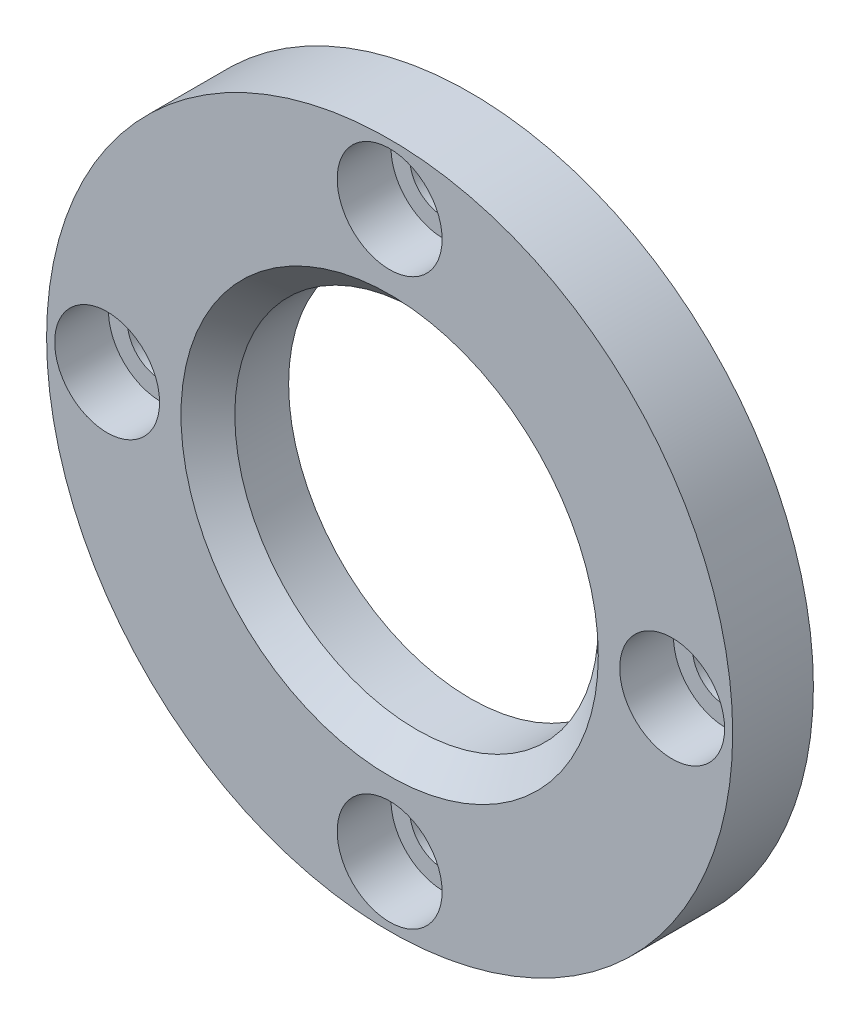
SolidWorks part; units mm, degrees
ref_plane "Спереди" through (0, 0, 0) normal (0, 0, 1) x (1, 0, 0)
ref_plane "Сверху" through (0, 0, 0) normal (0, 1, 0) x (1, 0, 0)
ref_plane "Справа" through (0, 0, 0) normal (1, 0, 0) x (0, 0, -1)
sketch "Эскиз1" plane through (0, 0, 0) normal (0, 0, 1) x (1, 0, 0)
  circle A0 centre (0, 0) radius 12.75
  circle A1 centre (0, 0) radius 10.5 construction
  circle A2 centre (0, 10.5) radius 1.25
  circle A3 centre (10.5, 0) radius 1.25
  circle A4 centre (0, -10.5) radius 1.25
  circle A5 centre (-10.5, 0) radius 1.25
  circle A6 centre (0, 0) radius 6.755
  dimension "D1" = 25.5
  dimension "D2" = 21
  dimension "D3" = 2.5
  dimension "D5" = 13.51
  dimension "D4" = 4
extrude "Бобышка-Вытянуть1" add sketch "Эскиз1" along normal blind 3
sketch "Эскиз2" plane through (0, 0, 3) normal (0, 0, 1) x (1, 0, 0)
  circle A0 centre (0, 10.5) radius 1.95
  circle A1 centre (10.5, 0) radius 1.95
  circle A2 centre (0, -10.5) radius 1.95
  circle A3 centre (-10.5, 0) radius 1.95
  circle A4 centre (10.5, 0) radius 1.25 construction
  dimension "D1" = 3.9
  dimension "D2" = 4
extrude "Вырез-Вытянуть1" cut sketch "Эскиз2" against normal blind 2
chamfer "Фаска1" distance 1 angle 45 1 edges at (6.755, 0, 3)
equation "\"print_offset\"= 0.5"
equation "\"radial_bearing_d1\"= 7.7"
equation "\"radial_bearing_d2\"= 16"
equation "\"radial_bearing_h\"= 5"
equation "\"shaft_d\"= 6"
equation "\"shaft_h\" = 60"
equation "\"central_hole_d\"= 20"
equation "\"sitting_screws_d\"= 34"
equation "\"screw_d\"= 2"
equation "\"screw_hh_d\"= 3.4"
equation "\"screw_h\"= 8"
equation "\"screw_hh_h\"= 2"
equation "\"motor_screw_d\"= 3"
equation "\"motor_screw_hh_d\"= 5.6"
equation "\"motor_screw_h\" = 20"
equation "\"motor_screw_hh_h\"= 2"
equation "\"motor_nut_d\"= 5.4"
equation "\"motor_nut_h\"= 2.8"
equation "\"D1@Эскиз1\"=\"radial_bearing_d2\"-\"print_offset\"+10"
equation "\"D2@Эскиз1\"=\"radial_bearing_d2\"+5"
equation "\"D3@Эскиз1\"=\"screw_d\"+\"print_offset\""
equation "\"D5@Эскиз1\"=\"radial_bearing_d2\"-(\"radial_bearing_d2\"-\"radial_bearing_d1\")*0.3"
equation "\"D1@Эскиз2\"=\"screw_hh_d\"+\"print_offset\""
equation "\"D1@Вырез-Вытянуть1\"=\"screw_hh_h\""
